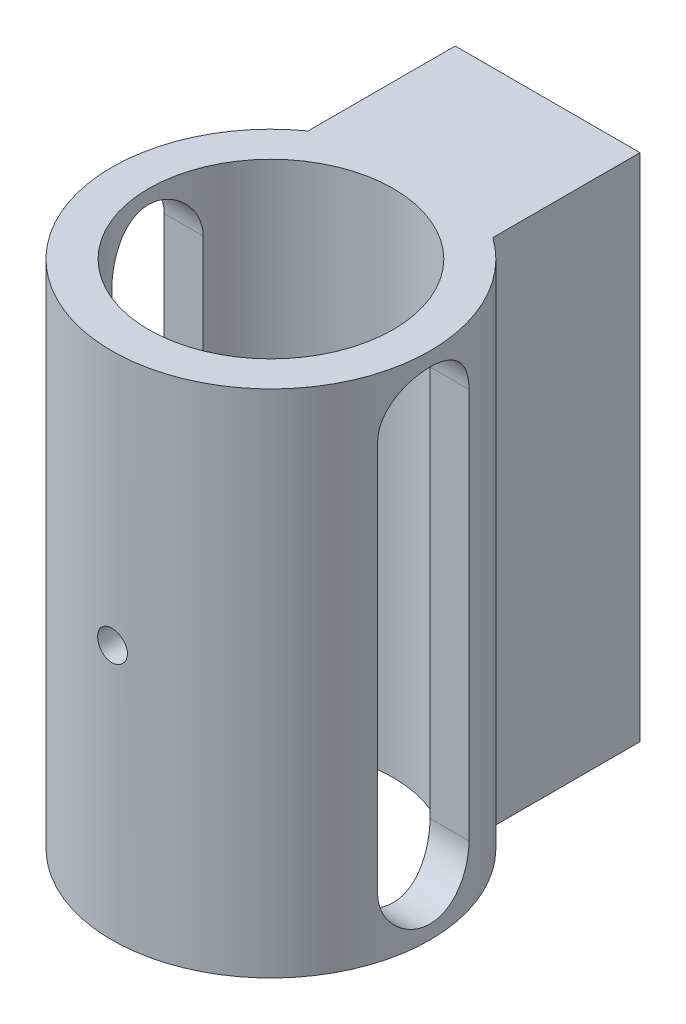
SolidWorks part; units mm, degrees
ref_plane "Front Plane" through (0, 0, 0) normal (0, 0, 1) x (1, 0, 0)
ref_plane "Top Plane" through (0, 0, 0) normal (0, 1, 0) x (1, 0, 0)
ref_plane "Right Plane" through (0, 0, 0) normal (1, 0, 0) x (0, 0, -1)
sketch "Sketch1" plane through (0, 0, 0) normal (0, 1, 0) x (1, 0, 0)
  circle A0 centre (0, 0) radius 8.8383
  circle A1 centre (0, 0) radius 11.5
  dimension "D1" = 17.6766
  dimension "D2" = 23
extrude "Boss-Extrude1" add sketch "Sketch1" along normal blind 36.88
ref_plane "Plane1" through (-11.5, 0, 0) normal (-1, 0, 0) x (0, 0, 1)
sketch "Sketch2" plane through (-11.5, 0, 0) normal (-1, 0, 0) x (0, 0, 1)
  line L0 (0, 32.5733) -> (0, 4.3067) construction
  line L1 (3.302, 32.5733) -> (3.302, 4.3067)
  line L2 (-3.302, 32.5733) -> (-3.302, 4.3067)
  line L3 (0, 32.5733) -> (0, 36.88) construction
  line L4 (8.8383, 36.88) -> (-8.8383, 36.88) construction
  line L5 (0, 4.3067) -> (0, 0) construction
  arc A0 (3.302, 32.5733) -> (-3.302, 32.5733) centre (0, 32.5733) ccw
  arc A1 (-3.302, 4.3067) -> (3.302, 4.3067) centre (0, 4.3067) ccw
  point P3 (0, 18.44)
  dimension "D1" = 3.302
extrude "Cut-Extrude1" cut sketch "Sketch2" against normal blind 55.88
sketch "Sketch3" plane through (0, 0, 0) normal (0, 0, 1) x (1, 0, 0)
  line L0 (0, 36.88) -> (0, 18.44) construction
  line L1 (11.5, 36.88) -> (-11.5, 36.88) construction
  circle A0 centre (0, 18.44) radius 1.0754
extrude "Cut-Extrude2" cut sketch "Sketch3" along normal through all
sketch "Sketch4" plane through (0, 0, 0) normal (0, 0, 1) x (1, 0, 0)
  line L0 (-8.8383, 0) -> (-6.6781, 0) construction
  line L5 (8.8383, 0) -> (6.6781, 0) construction
  line L6 (8.8383, 36.88) -> (6.6781, 36.88) construction
  line L7 (-8.8383, 36.88) -> (-6.6781, 36.88) construction
  line L9 (6.6781, 0) -> (-6.6781, 0)
  line L10 (6.6781, 0) -> (6.6781, 36.88)
  line L11 (6.6781, 36.88) -> (-6.6781, 36.88)
  line L12 (-6.6781, 0) -> (-6.6781, 36.88)
extrude "Boss-Extrude2" add sketch "Sketch4" along normal up to surface (10.6377 mm away) from offset 20 up to face at (11.2557, 18.44, 0) offset against normal yes
